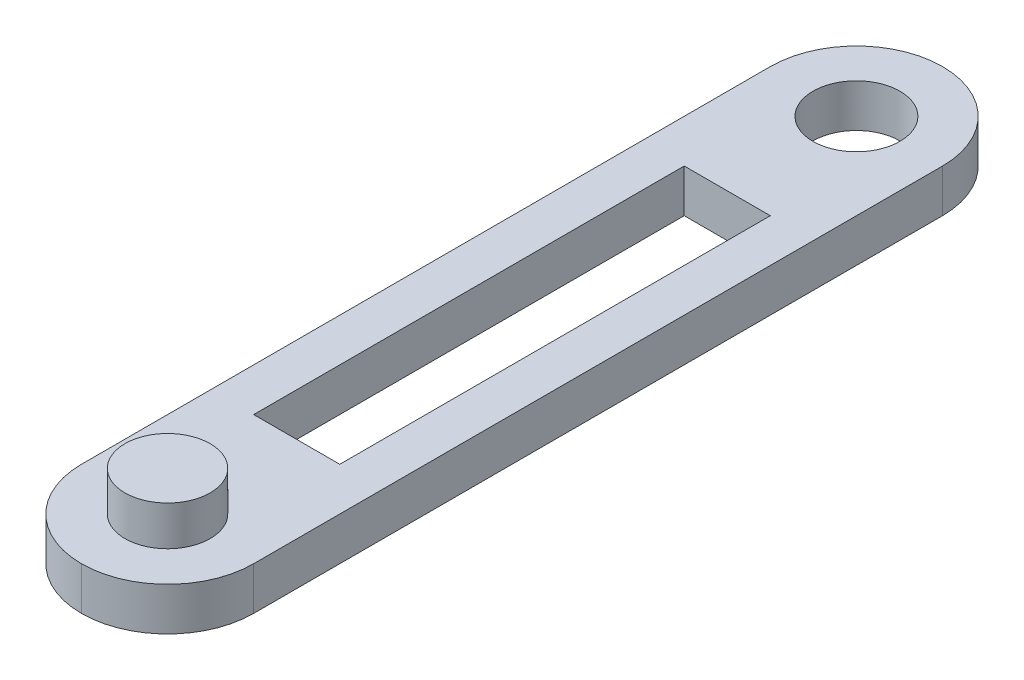
SolidWorks part; units mm, degrees
ref_plane "Front Plane" through (0, 0, 0) normal (0, 0, 1) x (1, 0, 0)
ref_plane "Top Plane" through (0, 0, 0) normal (0, 1, 0) x (1, 0, 0)
ref_plane "Right Plane" through (0, 0, 0) normal (1, 0, 0) x (0, 0, -1)
sketch "Sketch1" plane through (0, 0, 0) normal (0, 1, 0) x (1, 0, 0)
  line L0 (-23.3333, -31.0256) -> (-3.3333, -31.0256)
  line L2 (-23.3333, 68.9744) -> (-23.3333, -31.0256)
  line L4 (-3.3333, 68.9744) -> (-3.3333, -31.0256)
  line L5 (-23.3333, 68.9744) -> (-3.3333, 68.9744)
  dimension "D1" = 20
  dimension "D2" = 100
extrude "Boss-Extrude1" add sketch "Sketch1" along normal blind 5
fillet "Fillet1" radius 10 4 edges at (-23.3333, 2.5, -68.9744) (-3.3333, 2.5, -68.9744) (-23.3333, 2.5, 31.0256) (-3.3333, 2.5, 31.0256)
sketch "Sketch2" plane through (0, 5, 0) normal (0, 1, 0) x (1, 0, 0)
  circle A0 centre (-13.3333, 58.9744) radius 5.05
  circle A1 centre (-13.3333, -21.0256) radius 4.95
  dimension "D1" = 9.9
  dimension "D2" = 10.1
extrude "Boss-Extrude2" add sketch "Sketch2" along normal blind 4.6 contours A1
extrude "Cut-Extrude1" cut sketch "Sketch2<4>" against normal up to surface (5 mm away) contours A0 up to face at (-13.3333, 0, -18.9744)
sketch "Sketch2<4>" plane through (0, 5, 0) normal (0, 1, 0) x (1, 0, 0) same geometry as "Sketch2"
sketch "Sketch4" plane through (0, 5, 0) normal (0, 1, 0) x (1, 0, 0)
  line L0 (-3.3333, -21.0256) -> (-3.3333, 58.9744) construction
  line L1 (-18.3333, 43.9744) -> (-8.3333, 43.9744)
  line L2 (-18.3333, 43.9744) -> (-18.3333, -6.0256)
  line L3 (-18.3333, -6.0256) -> (-8.3333, -6.0256)
  line L4 (-8.3333, 43.9744) -> (-8.3333, -6.0256)
  circle A0 centre (-13.3333, 58.9744) radius 5.05 construction
  point P4 (-13.3333, 43.9744)
  dimension "D1" = 5
  dimension "D2" = 15
  dimension "D3" = 15
extrude "Cut-Extrude2" cut sketch "Sketch4" against normal up to surface (5 mm away) up to face at (-13.3333, 0, -64.0244)
